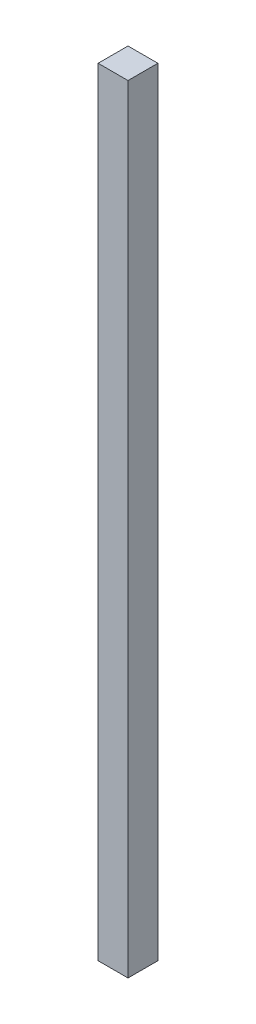
SolidWorks part; units mm, degrees
ref_plane "Plan de face" through (0, 0, 0) normal (0, 0, 1) x (1, 0, 0)
ref_plane "Plan de dessus" through (0, 0, 0) normal (0, 1, 0) x (1, 0, 0)
ref_plane "Plan de droite" through (0, 0, 0) normal (1, 0, 0) x (0, 0, -1)
sketch "Esquisse1" plane through (0, 0, 0) normal (0, 0, 1) x (1, 0, 0)
  line L1 (-21.9867, 13.5278) -> (-11.9867, 13.5278)
  line L2 (-21.9867, 13.5278) -> (-21.9867, -246.4722)
  line L3 (-21.9867, -246.4722) -> (-11.9867, -246.4722)
  line L4 (-11.9867, 13.5278) -> (-11.9867, -246.4722)
  dimension "D1" = 10
  dimension "D2" = 260
extrude "Boss.-Extru.1" add sketch "Esquisse1" along normal blind 10
equation "\"AA\"=31.7778"
equation "\"D2@Esquisse1\"= \"LargeurBoite\" - 20"
equation "\"EpaisseurPlaque\"= 3"
equation "\"ProfondeurBoite\"=460"
equation "\"LongueurSyphon\"=170"
equation "\"LargeurSyphon\"=120"
equation "\"HauteurCoteDroit\"= 490"
equation "\"HauteurCoteGauche\"= 540"
equation "\"HauteurSolSyphon\"= 300"
equation "\"HauteurSyphon\"=\"HauteurCoteGauche\"-\"HauteurSolSyphon\""
equation "\"LargeurDroite\"=10"
equation "\"LargeurGauche\"=150"
equation "\"LargeurBoite\"= \"LargeurDroite\" + \"LargeurGauche\" + \"LargeurSyphon\""
